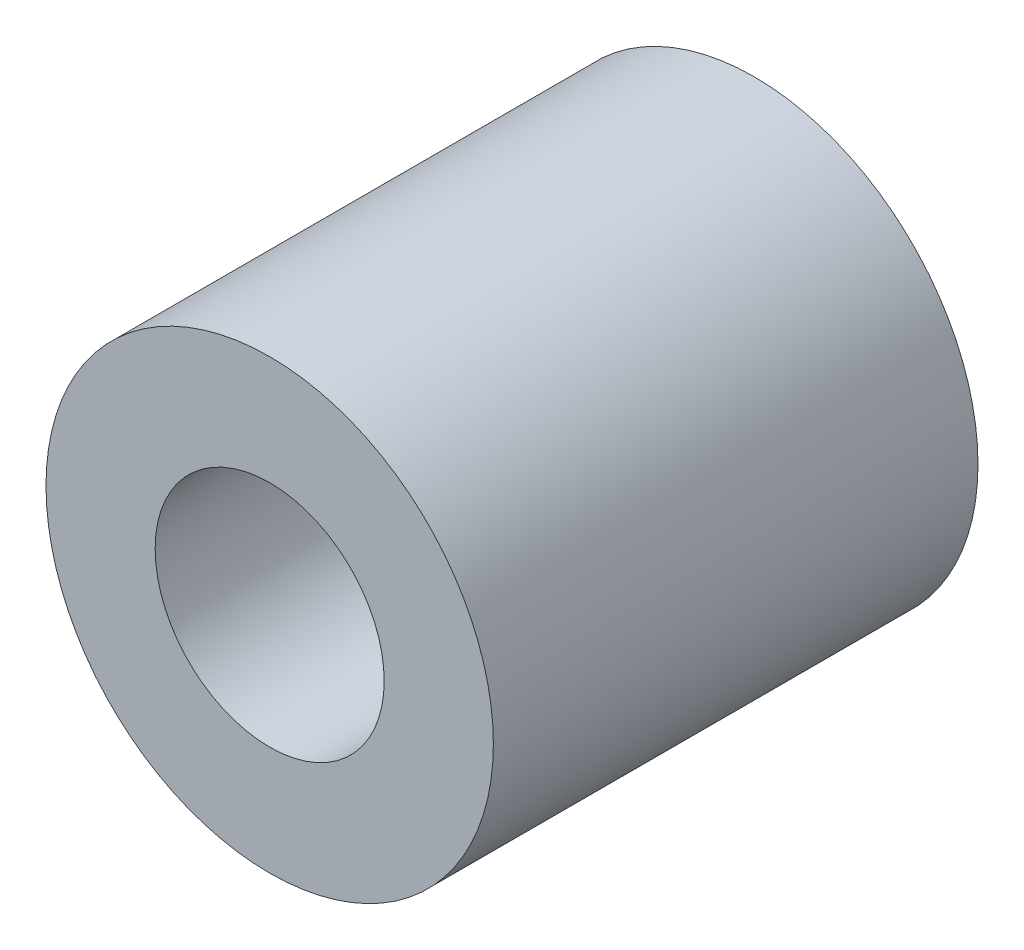
SolidWorks part; units mm, degrees
ref_plane "Front Plane" through (0, 0, 0) normal (0, 0, 1) x (1, 0, 0)
ref_plane "Top Plane" through (0, 0, 0) normal (0, 1, 0) x (1, 0, 0)
ref_plane "Right Plane" through (0, 0, 0) normal (1, 0, 0) x (0, 0, -1)
sketch "Sketch1" plane through (0, 0, 0) normal (0, 0, 1) x (1, 0, 0)
  circle A0 centre (0, 0) radius 4.7625
  circle A1 centre (0, 0) radius 2.4384
  dimension "OD" = 9.525
  dimension "ID" = 4.8768
extrude "Extrude1" add sketch "Sketch1" along normal mid plane 10.3187
sketch "Sketch2" plane through (0, 0, 0) normal (1, 0, 0) x (0, 0, -1)
  line L0 (-5.1594, -2.4384) -> (5.1594, -2.4384) construction
  line L3 (5.1594, 2.4384) -> (-5.1594, 2.4384) construction
  line L5 (-5.1594, -2.4384) -> (5.1594, -2.4384)
  line L6 (5.1594, 2.4384) -> (-5.1594, 2.4384)
sketch "Sketch4" plane through (0, 0, 5.1594) normal (0, 0, 1) x (1, 0, 0)
  line L0 (0, 0) -> (-1.7242, 1.7242)
  line L1 (0, -5.2388) -> (0, 5.2388) construction
  circle A0 centre (0, 0) radius 2.4384 construction
  dimension "D1" = 45
